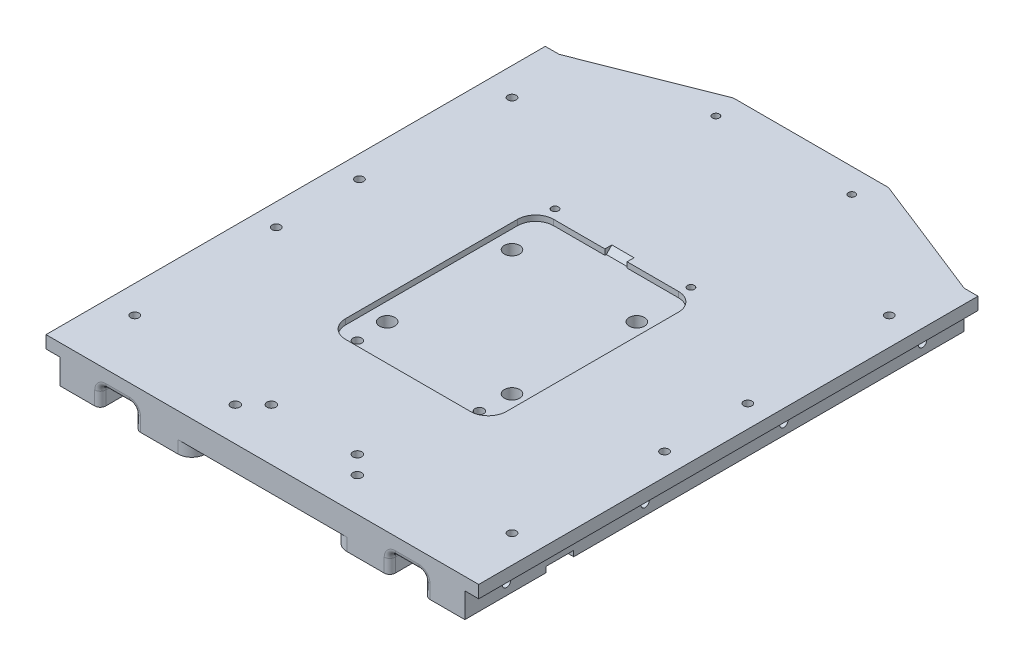
SolidWorks part; units mm, degrees
material "ABS"
ref_plane "Front Plane" through (0, 0, 0) normal (0, 0, 1) x (1, 0, 0)
ref_plane "Top Plane" through (0, 0, 0) normal (0, 1, 0) x (1, 0, 0)
ref_plane "Right Plane" through (0, 0, 0) normal (1, 0, 0) x (0, 0, -1)
sketch "Sketch1" plane through (0, 0, 0) normal (0, 1, 0) x (1, 0, 0)
  line L1 (73, 90) -> (-73, 90)
  line L2 (73, 90) -> (73, -90)
  line L3 (73, -90) -> (-73, -90)
  line L4 (-73, 90) -> (-73, -90)
  line L5 (73, 90) -> (-73, -90) construction
  line L6 (73, -90) -> (-73, 90) construction
  point P0 (0, 0)
  dimension "D1" = 146
  dimension "D2" = 180
extrude "Boss-Extrude1" add sketch "Sketch1" along normal blind 12
sketch "Sketch2" plane through (73, 0, 0) normal (1, 0, 0) x (0, 0, -1)
  line L0 (-90, 6) -> (90, 6) construction
  line L1 (-90, 12) -> (-90, 0) construction
  line L2 (90, 12) -> (90, 0) construction
hole_wizard "Ø3.0mm Dowel Hole1" positions "Sketch5" profile "Sketch6" hole size "Ø3.0" standard "ISO"
sketch "Sketch5" plane through (73, 0, 0) normal (1, 0, 0) x (0, 0, -1)
  line L1 (0, 6.6) -> (0, -6.6) construction
  line L2 (-90, 0) -> (90, 0) construction
  point P0 (-25, 4.5)
  point P12 (-75, 4.5)
  point P16 (75, 4.5)
  point P18 (25, 4.5)
  point P21 (-50, 4.5) [skipped]
  dimension "D1" = 25
  dimension "D3" = 4.5
  dimension "D4" = 50
  dimension "D2" = 3
sketch "Sketch6" plane through (73, 4.5, 25) normal (0, 1, 0) x (0, 0, -1)
  line L0 (0, 0) -> (0, 5.9013)
  line L1 (0, 5.9013) -> (1.5, 5)
  line L2 (1.5, 5) -> (1.5, 0)
  line L5 (1.5, 0) -> (0, 0)
  line L10 (0, 5.9013) -> (-1.5, 5) construction
  line L11 (0, -6.35) -> (0, 107.95) construction
  dimension "Hole Dia." = 3
  dimension "Hole Depth" = 5
  dimension "Drill Angle" = 118
mirror "Mirror1" about plane through (0, 0, 0) normal (1, 0, 0) of "Ø3.0mm Dowel Hole1"
sketch "Sketch7" plane through (0, 12, 0) normal (0, 1, 0) x (1, 0, 0)
  line L1 (70, 15) -> (-70, 15) construction
  line L2 (70, 15) -> (70, -15) construction
  line L3 (70, -15) -> (-70, -15) construction
  line L4 (-70, 15) -> (-70, -15) construction
  line L5 (70, 15) -> (-70, -15) construction
  line L6 (70, -15) -> (-70, 15) construction
  point P0 (0, 0)
  dimension "D1" = 30
  dimension "D2" = 140
hole_wizard "Ø3.0mm Dowel Hole2" positions "Sketch8" profile "Sketch9" hole size "Ø3.0" standard "ISO"
sketch "Sketch8" plane through (0, 12, 0) normal (0, 1, 0) x (1, 0, 0)
  line L1 (-73, 90) -> (-73, -90) construction
  point P0 (-70, 15)
  point P11 (70, 15)
  point P13 (70, -15)
  point P14 (-70, -15)
  point P16 (0, -15) [skipped]
  point P18 (0, 15) [skipped]
  dimension "D3" = 30
  dimension "D4" = 3
  dimension "D1" = 3
  dimension "D2" = 2
sketch "Sketch9" plane through (-70, 12, -15) normal (1, 0, 0) x (0, 0, 1)
  line L0 (0, 0) -> (0, 12)
  line L1 (0, 12) -> (1.5, 12)
  line L2 (1.5, 12) -> (1.5, 0)
  line L5 (1.5, 0) -> (0, 0)
  line L11 (0, -6.35) -> (0, 107.95) construction
  dimension "Thru Hole Dia." = 3
  dimension "Thru Hole Depth" = 12
sketch "Sketch10" plane through (0, 12, 0) normal (0, 1, 0) x (1, 0, 0)
  line L1 (-68, 68) -> (68, 68) construction
  line L2 (-68, 68) -> (-68, -68) construction
  line L3 (-68, -68) -> (68, -68) construction
  line L4 (68, 68) -> (68, -68) construction
  line L5 (-68, 68) -> (68, -68) construction
  line L6 (-68, -68) -> (68, 68) construction
  point P0 (0, 0)
  dimension "D1" = 136
hole_wizard "Ø3.0mm Dowel Hole3" positions "Sketch11" profile "Sketch12" hole size "Ø3.0" standard "ISO" end condition through all
sketch "Sketch11" plane through (0, 12, 0) normal (0, 1, 0) x (1, 0, 0)
  point P0 (-68, 68)
  point P3 (68, 68)
  point P6 (68, -68)
  point P9 (-68, -68)
sketch "Sketch12" plane through (-68, 12, -68) normal (1, 0, 0) x (0, 0, 1)
  line L0 (0, 0) -> (0, 12)
  line L1 (0, 12) -> (1.5, 12)
  line L2 (1.5, 12) -> (1.5, 0)
  line L5 (1.5, 0) -> (0, 0)
  line L11 (0, -6.35) -> (0, 107.95) construction
  dimension "Thru Hole Dia." = 3
  dimension "Thru Hole Depth" = 12
sketch "Sketch13" plane through (0, 12, 0) normal (0, 1, 0) x (1, 0, 0)
  line L16 (-73, -90) -> (73, -90) construction
  line L21 (-6.6, 0) -> (6.6, 0) construction
  line L22 (-24.5, 89) -> (24.5, 31) construction
  line L23 (-24.5, 31) -> (24.5, 89) construction
  line L24 (24.5, 31) -> (24.5, 89) construction
  line L25 (-24.5, 89) -> (24.5, 89) construction
  line L26 (-24.5, 31) -> (-24.5, 89) construction
  line L27 (-24.5, 31) -> (24.5, 31) construction
  line L28 (-28, 107.78) -> (28, 22.78) construction
  line L29 (-28, 22.78) -> (28, 107.78) construction
  line L30 (28, 22.78) -> (28, 107.78) construction
  line L31 (-28, 107.78) -> (28, 107.78) construction
  line L32 (-28, 22.78) -> (-28, 107.78) construction
  line L33 (-28, 22.78) -> (28, 22.78) construction
  line L34 (-73, 90) -> (73, 90)
  line L35 (28, 107.78) -> (73, 90)
  line L36 (-28, 107.78) -> (28, 107.78)
  line L37 (-73, 90) -> (-28, 107.78)
  point P27 (0, 60)
  point P28 (0, 65.28)
  dimension "D1" = 56
  dimension "D2" = 85
  dimension "D3" = 49
  dimension "D4" = 58
  dimension "D5" = 5.28
  dimension "D6" = 60
extrude "Boss-Extrude2" add sketch "Sketch13" against normal up to surface (12 mm away) up to face at (-68, 0, -66.5)
fillet "Fillet4" radius 3 2 edges at (-28, 6, -107.78) (28, 6, -107.78)
sketch "Sketch14" plane through (0, 12, 0) normal (0, 1, 0) x (1, 0, 0)
  line L0 (-30, 107.78) -> (30, 107.78)
  line L5 (-30, 107.78) -> (-30, 22.78)
  line L7 (30, 107.78) -> (30, 22.78)
  line L8 (27.4288, 107.78) -> (-27.4288, 107.78) construction
  line L18 (-30, 22.78) -> (30, 22.78)
  point P7 (0, 107.78)
  dimension "D1" = 85
  dimension "D2" = 60
extrude "Cut-Extrude1" cut sketch "Sketch14" along normal blind 7 from surface at -12 starting at face at (-68, 0, -66.5)
sketch "Sketch17" plane through (0, 7, 0) normal (0, -1, 0) x (-1, 0, 0)
  line L10 (30, 22.78) -> (30, 106.9898) construction
  line L11 (-30, 22.78) -> (30, 22.78) construction
  line L22 (-23.5, 99) -> (25.5, 41) construction
  line L23 (-23.5, 41) -> (25.5, 99) construction
  line L24 (25.5, 41) -> (25.5, 99) construction
  line L25 (-23.5, 99) -> (25.5, 99) construction
  line L26 (-23.5, 41) -> (-23.5, 99) construction
  line L27 (-23.5, 41) -> (25.5, 41) construction
  line L28 (-28, 117.78) -> (30, 32.78) construction
  line L29 (-28, 32.78) -> (30, 117.78) construction
  line L30 (30, 32.78) -> (30, 117.78) construction
  line L31 (-28, 117.78) -> (30, 117.78) construction
  line L32 (-28, 32.78) -> (-28, 117.78) construction
  line L33 (-28, 32.78) -> (30, 32.78) construction
  line L36 (-28, 117.78) -> (30, 117.78)
  circle A0 centre (25.5, 99) radius 1.25
  circle A1 centre (-23.5, 99) radius 1.25
  circle A2 centre (25.5, 41) radius 1.25
  circle A3 centre (-23.5, 41) radius 1.25
  point P1 (1, 74.8949)
  point P27 (1, 70)
  point P28 (1, 75.28)
  dimension "D6" = 2.5
  dimension "D1" = 58
  dimension "D2" = 85
  dimension "D3" = 49
  dimension "D4" = 58
  dimension "D5" = 5.28
  dimension "D7" = 10
extrude "Cut-Extrude2" cut sketch "Sketch17" against normal through all contours A1 | A0 | A2 | A3
sketch "Sketch19" plane through (0, 0, 0) normal (0, -1, 0) x (1, 0, 0)
  line L0 (30, -22.78) -> (-30, -22.78) construction
  line L1 (25.75, 30) -> (30, 30)
  line L2 (25.75, 30) -> (25.75, 50.75)
  line L3 (25.75, 81.5) -> (-25.75, 81.5)
  line L4 (-25.75, 30) -> (-25.75, 50.75)
  line L5 (25.75, 30) -> (-25.75, 81.5) construction
  line L6 (25.75, 81.5) -> (-25.75, 30) construction
  line L7 (15.25, 40.5) -> (-15.25, 40.5) construction
  line L8 (15.25, 40.5) -> (15.25, 71) construction
  line L9 (15.25, 71) -> (-15.25, 71) construction
  line L10 (-15.25, 40.5) -> (-15.25, 71) construction
  line L11 (15.25, 40.5) -> (-15.25, 71) construction
  line L12 (15.25, 71) -> (-15.25, 40.5) construction
  line L13 (-25.75, 60.75) -> (-25.75, 81.5)
  line L14 (30, -106.9898) -> (30, -22.78) construction
  line L15 (-30, -22.78) -> (30, -22.78)
  line L16 (-30, -22.78) -> (-30, 30)
  line L19 (30, -22.78) -> (30, 30)
  line L20 (-30, -22.78) -> (30, 30) construction
  line L21 (0, -6.6) -> (0, 6.6) construction
  line L22 (-30, 30) -> (30, -22.78) construction
  line L23 (-30, 30) -> (-25.75, 30)
  line L24 (73, 90) -> (73, -90) construction
  line L25 (73, 60.75) -> (25.75, 60.75)
  line L26 (73, 60.75) -> (73, 50.75)
  line L27 (73, 50.75) -> (25.75, 50.75)
  line L29 (73, 60.75) -> (25.75, 50.75) construction
  line L30 (73, 50.75) -> (25.75, 60.75) construction
  line L31 (25.75, 60.75) -> (25.75, 81.5)
  line L33 (-73, 50.75) -> (-25.75, 50.75)
  line L34 (-73, 60.75) -> (-73, 50.75)
  line L35 (-73, 60.75) -> (-25.75, 60.75)
  point P0 (0, 55.75)
  point P5 (0, 55.75)
  point P10 (0, 3.61)
  point P19 (49.375, 55.75)
  dimension "D1" = 51.5
  dimension "D2" = 30.5
  dimension "D3" = 30
  dimension "D5" = 10
  dimension "D6" = 51.5
extrude "Cut-Extrude3" cut sketch "Sketch19" against normal blind 2.5 contours L4 L1 L2 L3
sketch "Sketch20" plane through (0, 0, 0) normal (0, -1, 0) x (1, 0, 0)
  line L2 (25.75, 30) -> (-25.75, 30)
  line L3 (25.75, 30) -> (25.75, 81.5)
  line L7 (25.75, 81.5) -> (-25.75, 81.5)
  line L8 (-25.75, 30) -> (-25.75, 81.5)
  line L23 (25.75, 81.5) -> (-25.75, 81.5) construction
  line L24 (12.5, 90) -> (-12.5, 90)
  line L25 (12.5, 90) -> (12.5, 81.5)
  line L26 (12.5, 81.5) -> (-12.5, 81.5)
  line L27 (-12.5, 90) -> (-12.5, 81.5)
  line L28 (12.5, 90) -> (-12.5, 81.5) construction
  line L29 (12.5, 81.5) -> (-12.5, 90) construction
  line L30 (-73, 90) -> (73, 90) construction
  point P25 (0, 85.75)
  line M10 (73, 90) -> (-73, 90)
  line M20 (-25.75, 81.5) -> (25.75, 81.5)
  line M45 (-25.75, 60.75) -> (-25.75, 81.5)
  line M46 (25.75, 81.5) -> (25.75, 60.75)
  dimension "D4" = 25
extrude "Cut-Extrude4" cut sketch "Sketch20" against normal blind 5 contours L8 L2 L3 L7 M46 M20 M45 | L27 L7 L25 M10
chamfer "Chamfer1" distance 15 angle 45 4 edges at (-12.5, 2.5, 81.5) (12.5, 2.5, 81.5) (25.75, 1.25, 30) (-25.75, 1.25, 30)
chamfer "Chamfer2" distance 5 angle 45 4 edges at (-25.75, 1.25, 60.75) (-25.75, 1.25, 50.75) (25.75, 1.25, 50.75) (25.75, 1.25, 60.75)
sketch "Sketch21" plane through (0, 7, 0) normal (0, -1, 0) x (1, 0, 0)
  line L1 (22, 77.75) -> (-22, 77.75) construction
  line L2 (22, 77.75) -> (22, 33.75) construction
  line L3 (22, 33.75) -> (-22, 33.75) construction
  line L4 (-22, 77.75) -> (-22, 33.75) construction
  line L5 (22, 77.75) -> (-22, 33.75) construction
  line L6 (22, 33.75) -> (-22, 77.75) construction
  line L7 (15.5, 71.25) -> (-15.5, 71.25) construction
  line L8 (15.5, 71.25) -> (15.5, 40.25) construction
  line L9 (15.5, 40.25) -> (-15.5, 40.25) construction
  line L10 (-15.5, 71.25) -> (-15.5, 40.25) construction
  line L11 (15.5, 71.25) -> (-15.5, 40.25) construction
  line L12 (15.5, 40.25) -> (-15.5, 71.25) construction
  circle A0 centre (22, 33.75) radius 1.6
  circle A1 centre (-22, 33.75) radius 1.6
  circle A2 centre (-22, 77.75) radius 1.6
  circle A3 centre (22, 77.75) radius 1.6
  circle A4 centre (-15.5, 71.25) radius 1.6
  circle A5 centre (15.5, 71.25) radius 1.6
  circle A6 centre (15.5, 40.25) radius 1.6
  circle A7 centre (-15.5, 40.25) radius 1.6
  point P0 (0, 55.75)
  point P10 (0, 55.75)
  dimension "D2" = 3.2
  dimension "D1" = 44
  dimension "D3" = 31
extrude "Cut-Extrude5" cut sketch "Sketch21" along normal through all from surface at -5 contours A1 | A4 | A2 | A0 | A5 | A3 starting at face at (23.5, 12, -42.25)
fillet "Fillet1" radius 5 10 edges at (30.75, 1.25, 50.75) (25.75, 1.25, 45.75) (30.75, 1.25, 60.75) (25.75, 1.25, 65.75) (-30.75, 1.25, 50.75) (-25.75, 1.25, 45.75) (-30.75, 1.25, 60.75) (-25.75, 1.25, 65.75) (-19, 2.5, 90) (19, 2.5, 90)
fillet "Fillet5" radius 0.5 4 edges at (-25.75, 2.5, 83.25) (25.75, 2.5, 83.25) (-25.75, 3.75, 30) (25.75, 3.75, 30)
sketch "Sketch24" plane through (0, 0, 0) normal (0, -1, 0) x (1, 0, 0)
  line L5 (6.25, -18.78) -> (6.25, -26.78)
  line L6 (6.25, -18.78) -> (-6.25, -18.78)
  line L7 (6.25, -26.78) -> (-6.25, -26.78)
  line L8 (-6.25, -18.78) -> (-6.25, -26.78)
  line L9 (6.25, -18.78) -> (-6.25, -26.78) construction
  line L10 (6.25, -26.78) -> (-6.25, -18.78) construction
  line L11 (-30, -22.78) -> (30, -22.78) construction
  point P1 (0, -22.78)
  dimension "D1" = 12.5
  dimension "D2" = 8
extrude "Cut-Extrude7" cut sketch "Sketch24" against normal up to surface (7 mm away) up to face at (23.5, 7, -42.25)
chamfer "Chamfer3" distance 2.5 angle 45 1 edges at (0, 2.5, -18.78)
fillet "Fillet6" radius 1 2 edges at (30, 3.5, -106.9898) (-30, 3.5, -106.9898)
sketch "Sketch25" plane through (0, 0, 0) normal (0, -1, 0) x (1, 0, 0)
  line L1 (-58.4337, 90) -> (-45.9337, 90)
  line L2 (-58.4337, 90) -> (-58.4337, -100.6942)
  line L3 (-58.4337, -100.6942) -> (-45.9337, -100.6942)
  line L4 (-45.9337, 90) -> (-45.9337, -100.6942)
  line L5 (-31.3675, -106.4495) -> (-73, -90) construction
  line L6 (-52.1837, -98.2247) -> (-52.1837, -117.3365) construction
  line L7 (0, -6.6) -> (0, 6.6) construction
  line L8 (45.9337, 90) -> (45.9337, -100.6942)
  line L9 (58.4337, -100.6942) -> (45.9337, -100.6942)
  line L10 (58.4337, 90) -> (58.4337, -100.6942)
  line L11 (58.4337, 90) -> (45.9337, 90)
  point P12 (-52.1837, -100.6942)
  dimension "D1" = 12.5
extrude "Cut-Extrude8" cut sketch "Sketch25" against normal blind 7.5
sketch "Sketch26" plane through (0, 0, 0) normal (0, -1, 0) x (1, 0, 0)
  line L0 (-30, 40.75) -> (-30, -105.5194) construction
  line L1 (-45.9337, -55.28) -> (-30, -55.28)
  line L2 (-45.9337, -55.28) -> (-45.9337, -40.28)
  line L3 (-45.9337, -40.28) -> (-30, -40.28)
  line L4 (-30, -55.28) -> (-30, -40.28)
  line L5 (-45.9337, -55.28) -> (-30, -40.28) construction
  line L6 (-45.9337, -40.28) -> (-30, -55.28) construction
  line L7 (-45.9337, -100.6942) -> (-45.9337, 50.75) construction
  line L8 (-30, -22.78) -> (-6.25, -22.78) construction
  line L9 (0, -6.6) -> (0, 6.6) construction
  line L10 (45.9337, -40.28) -> (30, -40.28)
  line L11 (30, -55.28) -> (30, -40.28)
  line L12 (45.9337, -55.28) -> (30, -55.28)
  line L13 (45.9337, -55.28) -> (45.9337, -40.28)
  point P0 (-37.9669, -47.78)
  dimension "D1" = 15
  dimension "D2" = 25
extrude "Cut-Extrude9" cut sketch "Sketch26" against normal up to surface (7 mm away) up to face at (0, 7, -70.2961)
sketch "Sketch22" plane through (0, 0, 0) normal (0, -1, 0) x (1, 0, 0)
  line L5 (62.5, 17.5) -> (73, 26)
  line L6 (-62.5, 22.5) -> (62.5, 22.5)
  line L7 (-62.5, 22.5) -> (-62.5, 7.5) construction
  line L12 (-62.5, 7.5) -> (62.5, 7.5)
  line L13 (62.5, 22.5) -> (62.5, 7.5) construction
  line L14 (-62.5, 22.5) -> (62.5, 7.5) construction
  line L15 (-62.5, 7.5) -> (62.5, 22.5) construction
  line L16 (-62.5, 12.5) -> (62.5, 12.5)
  line L17 (-62.5, 12.5) -> (-62.5, 17.5) construction
  line L18 (-62.5, 17.5) -> (62.5, 17.5)
  line L19 (62.5, 12.5) -> (62.5, 17.5) construction
  line L20 (-62.5, 12.5) -> (62.5, 17.5) construction
  line L21 (-62.5, 17.5) -> (62.5, 12.5) construction
  line L22 (73, 90) -> (73, 60.75) construction
  line L23 (73, 26) -> (73, 31)
  line L24 (73, 31) -> (62.5, 22.5)
  line L25 (0, 15) -> (40.3645, 15) construction
  line L26 (62.5, 12.5) -> (73, 4)
  line L27 (73, -1) -> (62.5, 7.5)
  line L28 (0, -6.6) -> (0, 6.6) construction
  line L29 (-73, -1) -> (-62.5, 7.5)
  line L30 (-62.5, 12.5) -> (-73, 4)
  line L31 (-62.5, 17.5) -> (-73, 26)
  line L32 (-73, 26) -> (-73, 31)
  line L33 (-73, 31) -> (-62.5, 22.5)
  line L34 (73, -1) -> (73, 4)
  line L35 (-73, -1) -> (-73, 4)
  point P0 (70, 15)
  dimension "D1" = 15
  dimension "D2" = 125
  dimension "D3" = 5
  dimension "D4" = 8.5
fillet "Fillet7" radius 2 16 edges at (58.4337, 3.75, -95.7553) (45.9337, 3.75, -100.6942) (45.9337, 3.75, 90) (58.4337, 3.75, 90) (-45.9337, 3.75, -100.6942) (-58.4337, 3.75, -95.7553) (-58.4337, 3.75, 90) (-45.9337, 3.75, 90) (52.1837, 7.5, -98.2247) (45.9337, 7.5, -5.3471) (52.1837, 7.5, 90) (58.4337, 7.5, -2.8776) (-52.1837, 7.5, -98.2247) (-58.4337, 7.5, -2.8776) (-52.1837, 7.5, 90) (-45.9337, 7.5, -5.3471)
sketch "Sketch29" plane through (0, 12, 0) normal (0, 1, 0) x (1, 0, 0)
  line L0 (0, -6.6) -> (0, 6.6) construction
  line L1 (73, 90) -> (78, 90)
  line L3 (73, -90) -> (78, -90)
  line L4 (78, 90) -> (78, -90)
  line L5 (-73, -90) -> (-78, -90)
  line L7 (27.4288, 107.78) -> (-27.4288, 107.78)
  line L18 (-28.5312, 107.5701) -> (-73, 90)
  line L19 (-73, 90) -> (-73, -90)
  line L20 (-73, -90) -> (73, -90)
  line L21 (73, -90) -> (73, 90)
  line L22 (73, 90) -> (28.5312, 107.5701)
  line L23 (27.4288, 107.78) -> (-27.4288, 107.78)
  line L24 (-28.5312, 107.5701) -> (-73, 90)
  line L26 (-73, -90) -> (73, -90)
  line L28 (73, 90) -> (28.5312, 107.5701)
  line L29 (-78, 90) -> (-78, -90)
  line L30 (-73, 90) -> (-78, 90)
  circle A0 centre (-15.5, -71.25) radius 1.6 construction
  circle A1 centre (-70, -15) radius 1.5
  circle A6 centre (-70, -15) radius 1.5
  circle A7 centre (70, -15) radius 1.5
  circle A8 centre (70, -15) radius 1.5
  circle A9 centre (70, 15) radius 1.5
  circle A10 centre (70, 15) radius 1.5
  circle A11 centre (-70, 15) radius 1.5
  circle A12 centre (-70, 15) radius 1.5
  circle A13 centre (-68, -68) radius 1.5
  circle A14 centre (-68, -68) radius 1.5
  circle A15 centre (68, -68) radius 1.5
  circle A16 centre (68, -68) radius 1.5
  circle A17 centre (68, 68) radius 1.5
  circle A18 centre (68, 68) radius 1.5
  circle A19 centre (-68, 68) radius 1.5
  circle A20 centre (-68, 68) radius 1.5
  circle A21 centre (23.5, 99) radius 1.25
  circle A22 centre (23.5, 99) radius 1.25
  circle A23 centre (-25.5, 99) radius 1.25
  circle A24 centre (-25.5, 99) radius 1.25
  circle A25 centre (-25.5, 41) radius 1.25
  circle A26 centre (-25.5, 41) radius 1.25
  circle A27 centre (23.5, 41) radius 1.25
  circle A28 centre (23.5, 41) radius 1.25
  circle A29 centre (-22, -33.75) radius 1.6
  circle A30 centre (-22, -33.75) radius 1.6
  circle A31 centre (22, -77.75) radius 1.6
  circle A32 centre (22, -77.75) radius 1.6
  circle A33 centre (-22, -77.75) radius 1.6
  circle A34 centre (-22, -77.75) radius 1.6
  circle A35 centre (22, -33.75) radius 1.6
  circle A36 centre (22, -33.75) radius 1.6
  circle A37 centre (15.5, -71.25) radius 1.6 construction
  arc A38 (-27.4288, 107.78) -> (-28.5312, 107.5701) centre (-27.4288, 104.78) ccw
  arc A39 (28.5312, 107.5701) -> (27.4288, 107.78) centre (27.4288, 104.78) ccw
  arc A40 (-27.4288, 107.78) -> (-28.5312, 107.5701) centre (-27.4288, 104.78) ccw
  arc A41 (28.5312, 107.5701) -> (27.4288, 107.78) centre (27.4288, 104.78) ccw
  circle A42 centre (-15.5, -71.25) radius 1.6
  circle A43 centre (15.5, -71.25) radius 1.6
  dimension "D18" = 5
  dimension "D1" = 0
  dimension "D2" = 0
  dimension "D3" = 0
  dimension "D4" = 0
  dimension "D5" = 0
  dimension "D6" = 0
  dimension "D7" = 0
  dimension "D8" = 0
  dimension "D9" = 0
  dimension "D10" = 0
  dimension "D11" = 0
  dimension "D12" = 0
  dimension "D13" = 0
  dimension "D14" = 0
  dimension "D15" = 0
  dimension "D16" = 0
  dimension "D17" = 0
extrude "Boss-Extrude3" add sketch "Sketch29" along normal blind 2
sketch "Sketch28" plane through (0, 0, 0) normal (0, 1, 0) x (1, 0, 0)
  line L0 (-4, 37.5) -> (-4, 35) construction
  line L6 (4, 37.5) -> (4, 40)
  line L7 (-22.5, -37.5) -> (22.5, -37.5)
  line L8 (-29, -31) -> (-29, 31)
  line L9 (-22.5, 37.5) -> (-4, 37.5)
  line L10 (29, -31) -> (29, 31)
  line L11 (-29, -37.5) -> (29, 37.5) construction
  line L12 (-29, 37.5) -> (29, -37.5) construction
  line L13 (4, 40) -> (-4, 40)
  line L14 (-4, 37.5) -> (-4, 40)
  line L15 (4, 35) -> (-4, 40) construction
  line L16 (4, 40) -> (-4, 35) construction
  line L17 (-4, 35) -> (4, 35) construction
  line L18 (4, 35) -> (4, 37.5) construction
  line L20 (4, 37.5) -> (22.5, 37.5)
  line L21 (-4, 37.5) -> (0, 37.5) construction
  line L22 (0, 37.5) -> (4, 37.5) construction
  arc A4 (-22.5, -37.5) -> (-29, -31) centre (-22.5, -31) cw
  arc A5 (-29, 31) -> (-22.5, 37.5) centre (-22.5, 31) cw
  arc A6 (22.5, 37.5) -> (29, 31) centre (22.5, 31) cw
  arc A7 (22.5, -37.5) -> (29, -31) centre (22.5, -31) ccw
  point P0 (0, 37.5)
  point P1 (0, 0)
  dimension "D1" = 75
  dimension "D2" = 6.5
  dimension "D4" = 8
  dimension "D3" = 58
  dimension "D5" = 5
extrude "Cut-Extrude10" cut sketch "Sketch28" against normal blind 2 from surface at 14 starting at face at (-15.5, 14, 72.85)
sketch "Sketch31" plane through (0, 0, 0) normal (0, 1, 0) x (1, 0, 0)
  line L0 (0, 0) -> (0, -144.8626) construction
  point P0 (-22.5, -113.5)
  point P3 (22.5, -113.5)
  point P9 (22.5, 113.5)
  point P24 (-22.5, 22.5)
  point P27 (22.5, 22.5)
  point P30 (22.5, -22.5)
  point P33 (-22.5, -22.5)
  point P41 (-24, 95)
  point P44 (24, 95)
  point P47 (-22.5, -93.5)
  point P50 (22.5, -93.5)
  point P53 (-22.5, 113.5)
  dimension "D1" = 45
  dimension "D2" = 20
sketch "Sketch32" plane through (0, 12, 0) normal (0, 1, 0) x (1, 0, 0)
  circle A0 centre (-22.5, 22.5) radius 2.75
  circle A1 centre (22.5, 22.5) radius 2.75
  circle A2 centre (22.5, -22.5) radius 2.75
  circle A3 centre (-22.5, -22.5) radius 2.75
  dimension "D1" = 5.5
extrude "Cut-Extrude11" cut sketch "Sketch32" against normal blind 4
chamfer "Chamfer4" distance 2 angle 45 1 edges at (0, 12, -40)
sketch "Sketch33" plane through (0, 0, 0) normal (0, -1, 0) x (1, 0, 0)
  line L5 (-30.4337, 88) -> (-43.9337, 88)
  line L6 (-30.4337, 88) -> (-43.9337, 88)
  line L8 (-43.9337, 88) -> (-43.9337, 62.75)
  line L10 (-43.9337, 88) -> (-43.9337, 62.75)
  line L12 (32, -104.0491) -> (43.9337, -99.334)
  line L13 (43.9337, -99.334) -> (43.9337, -57.28)
  line L14 (43.9337, -57.28) -> (32, -57.28)
  line L15 (32, -57.28) -> (32, -104.0491)
  line L16 (32, -104.0491) -> (43.9337, -99.334)
  line L17 (43.9337, -99.334) -> (43.9337, -57.28)
  line L18 (43.9337, -57.28) -> (32, -57.28)
  line L19 (32, -57.28) -> (32, -104.0491)
  line L20 (-43.9337, 62.75) -> (-32.8211, 62.75)
  line L22 (-43.9337, 62.75) -> (-32.8211, 62.75)
  line L24 (-43.9337, -57.28) -> (-43.9337, -99.334)
  line L25 (-43.9337, -99.334) -> (-32, -104.0491)
  line L26 (-32, -104.0491) -> (-32, -57.28)
  line L27 (-32, -57.28) -> (-43.9337, -57.28)
  line L28 (-43.9337, -57.28) -> (-43.9337, -99.334)
  line L29 (-43.9337, -99.334) -> (-32, -104.0491)
  line L30 (-32, -104.0491) -> (-32, -57.28)
  line L31 (-32, -57.28) -> (-43.9337, -57.28)
  line L32 (-30.6997, 63.6287) -> (-28.6287, 65.6997)
  line L34 (43.9337, 62.75) -> (43.9337, 88)
  line L36 (43.9337, 62.75) -> (43.9337, 88)
  line L38 (43.9337, 88) -> (30.4337, 88)
  line L46 (43.9337, 88) -> (30.4337, 88)
  line L48 (27.75, 83.1619) -> (27.75, 67.8211)
  line L50 (27.75, 83.1619) -> (27.75, 67.8211)
  line L52 (-30.6997, 63.6287) -> (-28.6287, 65.6997)
  line L53 (-27.75, 67.8211) -> (-27.75, 83.1619)
  line L54 (-27.75, 67.8211) -> (-27.75, 83.1619)
  line L55 (28.6287, 65.6997) -> (30.6997, 63.6287)
  line L56 (28.6287, 65.6997) -> (30.6997, 63.6287)
  line L57 (32.8211, 62.75) -> (43.9337, 62.75)
  line L64 (32.8211, 62.75) -> (43.9337, 62.75)
  arc A2 (-32.8211, 62.75) -> (-30.6997, 63.6287) centre (-32.8211, 65.75) ccw
  arc A4 (-32.8211, 62.75) -> (-30.6997, 63.6287) centre (-32.8211, 65.75) ccw
  arc A6 (27.75, 67.8211) -> (28.6287, 65.6997) centre (30.75, 67.8211) ccw
  arc A11 (27.75, 67.8211) -> (28.6287, 65.6997) centre (30.75, 67.8211) ccw
  arc A20 (-28.6287, 65.6997) -> (-27.75, 67.8211) centre (-30.75, 67.8211) ccw
  arc A21 (-28.6287, 65.6997) -> (-27.75, 67.8211) centre (-30.75, 67.8211) ccw
  arc A22 (-27.6062, 83.9974) -> (-30.4337, 88) centre (-30.4337, 85) ccw
  arc A23 (-27.6062, 83.9974) -> (-30.4337, 88) centre (-30.4337, 85) ccw
  arc A24 (-27.6062, 83.9974) -> (-27.75, 83.1619) centre (-25.25, 83.1619) ccw
  arc A28 (-27.6062, 83.9974) -> (-27.75, 83.1619) centre (-25.25, 83.1619) ccw
  arc A29 (30.6997, 63.6287) -> (32.8211, 62.75) centre (32.8211, 65.75) ccw
  arc A30 (30.6997, 63.6287) -> (32.8211, 62.75) centre (32.8211, 65.75) ccw
  arc A31 (30.4337, 88) -> (27.6062, 83.9974) centre (30.4337, 85) ccw
  arc A32 (30.4337, 88) -> (27.6062, 83.9974) centre (30.4337, 85) ccw
  arc A33 (27.75, 83.1619) -> (27.6062, 83.9974) centre (25.25, 83.1619) ccw
  arc A34 (27.75, 83.1619) -> (27.6062, 83.9974) centre (25.25, 83.1619) ccw
  dimension "D1" = 2
  dimension "D2" = 2
  dimension "D3" = 2
  dimension "D4" = 2
sketch "Sketch35" plane through (0, 0, 0) normal (0, -1, 0) x (1, 0, 0)
  line L9 (35.75, -38.28) -> (35.75, 48.75)
  line L10 (0, -7.7) -> (0, 7.7) construction
  line L11 (-35.75, -38.28) -> (-35.75, 48.75)
  line L12 (-43.25, 48.75) -> (-35.75, 48.75)
  line L13 (-43.25, -38.28) -> (-43.25, 48.75)
  line L14 (-35.75, -38.28) -> (-43.25, -38.28)
  line L18 (32, -38.28) -> (43.25, -38.28)
  line L19 (43.25, -38.28) -> (43.25, 48.75)
  line L20 (43.25, 48.75) -> (32.8211, 48.75)
  line L21 (30.6997, 47.8713) -> (28.6287, 45.8003)
  line L22 (27.75, 43.6789) -> (27.75, 25.3211)
  line L23 (25.6997, 20.3713) -> (20.3787, 15.0503)
  line L24 (19.5, 12.9289) -> (19.5, -6.9516)
  line L25 (19.5, -6.9516) -> (32, -19.4516)
  line L26 (32, -19.4516) -> (32, -38.28)
  line L27 (35.75, -38.28) -> (43.25, -38.28)
  line L28 (43.25, -38.28) -> (43.25, 48.75)
  line L29 (43.25, 48.75) -> (35.75, 48.75)
  arc A8 (32.8211, 48.75) -> (30.6997, 47.8713) centre (32.8211, 45.75) ccw
  arc A9 (28.6287, 45.8003) -> (27.75, 43.6789) centre (30.75, 43.6789) ccw
  arc A10 (25.6997, 20.3713) -> (27.75, 25.3211) centre (20.75, 25.3211) ccw
  arc A11 (20.3787, 15.0503) -> (19.5, 12.9289) centre (22.5, 12.9289) ccw
  dimension "D2" = 7.5
  dimension "D1" = 2
sketch "Sketch34" plane through (0, 12, 0) normal (0, -1, 0) x (1, 0, 0)
  line L4 (-78, -90) -> (-73, -90)
  line L5 (-73, -90) -> (-73, 90)
  line L6 (-73, 90) -> (-78, 90)
  line L7 (-78, 90) -> (-78, -90)
  line L8 (-78, -90) -> (-73, -90)
  line L9 (-73, -90) -> (-73, 90)
  line L10 (-73, 90) -> (-78, 90)
  line L11 (-78, 90) -> (-78, -90)
  line L12 (78, 90) -> (73, 90)
  line L13 (73, 90) -> (73, -90)
  line L14 (73, -90) -> (78, -90)
  line L15 (78, -90) -> (78, 90)
  line L16 (78, 90) -> (73, 90)
  line L17 (73, 90) -> (73, -90)
  line L18 (73, -90) -> (78, -90)
  line L19 (78, -90) -> (78, 90)
  dimension "D1" = 0
  dimension "D2" = 0
extrude "Boss-Extrude4" add sketch "Sketch34" along normal blind 2.5
sketch "Sketch36" plane through (0, 0, 0) normal (0, -1, 0) x (1, 0, 0)
  line L172 (-27.4288, -107.78) -> (27.4288, -107.78) construction
  line L173 (78, 90) -> (-78, 90)
  line L174 (78, 90) -> (78, -107.78)
  line L175 (78, -107.78) -> (-78, -107.78)
  line L177 (-78, 90) -> (-78, -107.78)
  line L184 (-78, 90) -> (-78, -90) construction
extrude "Cut-Extrude14" cut sketch "Sketch36" against normal blind 0.5
